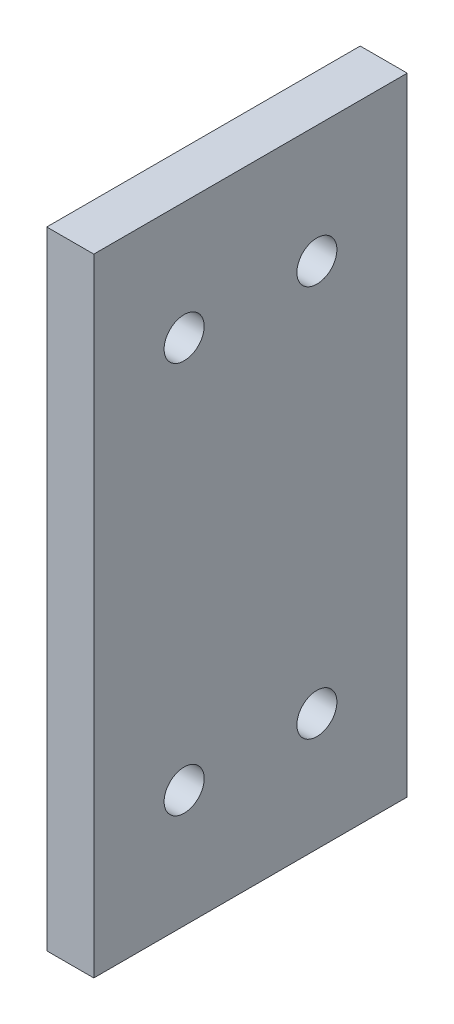
SolidWorks part; units mm, degrees
ref_plane "Front Plane" through (0, 0, 0) normal (1, 0, 0) x (0, 1, 0)
ref_plane "Top Plane" through (0, 0, 0) normal (0, 0, 1) x (0, 1, 0)
ref_plane "Right Plane" through (0, 0, 0) normal (0, 1, 0) x (-1, 0, 0)
sketch "Sketch1" plane through (0, 0, 0) normal (1, 0, 0) x (0, 1, 0)
  line L7 (-40, -20) -> (40, -20)
  line L8 (-40, -20) -> (-40, 20)
  line L9 (-40, 20) -> (40, 20)
  line L10 (40, -20) -> (40, 20)
  line L11 (-40, -20) -> (40, 20) construction
  line L12 (-40, 20) -> (40, -20) construction
  line L13 (-25, -8.47) -> (25, -8.47) construction
  line L14 (-25, -8.47) -> (-25, 8.47) construction
  line L15 (-25, 8.47) -> (25, 8.47) construction
  line L16 (25, -8.47) -> (25, 8.47) construction
  line L17 (-25, -8.47) -> (25, 8.47) construction
  line L18 (-25, 8.47) -> (25, -8.47) construction
  circle A0 centre (-25, 8.47) radius 2.555
  circle A1 centre (-25, -8.47) radius 2.555
  circle A2 centre (25, -8.47) radius 2.555
  circle A3 centre (25, 8.47) radius 2.555
  point P0 (0, 0)
  point P2 (0, 0)
  dimension "D5" = 5.11
  dimension "D6" = 5.11
  dimension "D7" = 5.11
  dimension "D8" = 5.11
  dimension "D1" = 80
  dimension "D2" = 40
  dimension "D3" = 11.53
  dimension "D4" = 50
extrude "Boss-Extrude2" add sketch "Sketch1" along normal blind 6 contours L7 L10 L9 L8
extrude "Cut-Extrude3" cut sketch "Sketch1<3>" along normal up to next contours A0 | A3 | A2 | A1
sketch "Sketch1<3>" plane through (0, 0, 0) normal (1, 0, 0) x (0, 1, 0) same geometry as "Sketch1"
